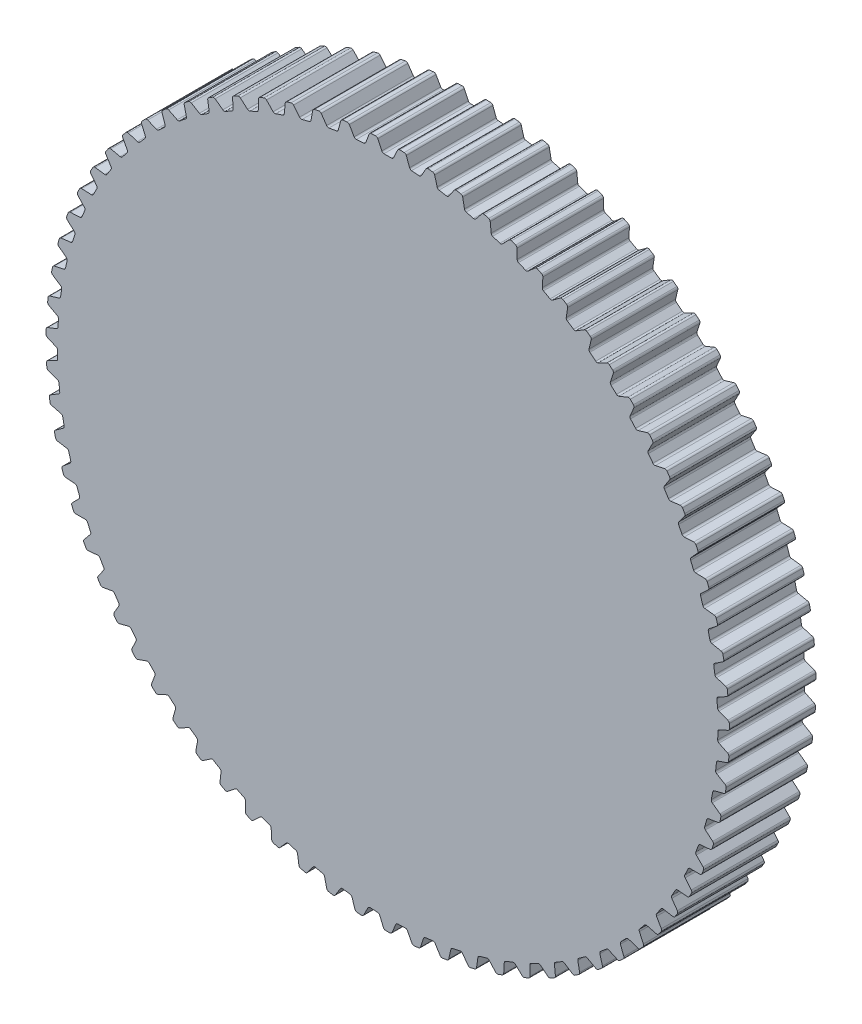
SolidWorks part; units mm, degrees
ref_plane "Ebene vorne" through (0, 0, 0) normal (0, 0, 1) x (1, 0, 0)
ref_plane "Ebene oben" through (0, 0, 0) normal (0, 1, 0) x (1, 0, 0)
ref_plane "Ebene rechts" through (0, 0, 0) normal (1, 0, 0) x (0, 0, -1)
ref_axis "Achse" through (0, 0, 4.125) along (0, 0, -1)
sketch "Skizze1" plane through (0, 0, 0) normal (0, 0, 1) x (1, 0, 0)
  circle A0 centre (0, 0) radius 29.6
  circle A1 centre (0, 0) radius 30.2 construction
  dimension "D1" = 0.6
  dimension "d0" = 59.2
  dimension "D2" = 60.4
extrude "Aufsatz-Linear austragen1" add sketch "Skizze1" along normal mid plane 7.5 contours A0 region at (0, 0, 0)
sketch "Skizze2" plane through (0, 0, 3.75) normal (0, 0, 1) x (1, 0, 0)
  line L0 (-0.8592, 29.4661) -> (-0.5091, 28.7155)
  line L1 (-0.3279, 28.6) -> (0.3279, 28.6)
  line L2 (0.5091, 28.7155) -> (0.8592, 29.4661)
  line L3 (0, 28.6) -> (0, 0) construction
  line L4 (-0.8592, 29.4661) -> (-0.915, 29.5859) construction
  line L5 (0.8592, 29.4661) -> (0.915, 29.5859) construction
  circle A0 centre (0, 0) radius 29.6 construction
  arc A1 (0.3279, 28.6) -> (0.5091, 28.7155) centre (0.3279, 28.8) ccw
  arc A2 (-0.5091, 28.7155) -> (-0.3279, 28.6) centre (-0.3279, 28.8) ccw
  arc A3 (-1.0475, 29.5815) -> (1.0475, 29.5815) centre (0, 0) ccw
  arc A4 (0.8592, 29.4661) -> (1.0475, 29.5815) centre (1.0404, 29.3816) cw
  arc A5 (-0.8592, 29.4661) -> (-1.0475, 29.5815) centre (-1.0404, 29.3816) ccw
  arc A6 (-1.0475, 29.5815) -> (1.0475, 29.5815) centre (0, 0) cw construction
  point P9 (0, 29.6)
  point P16 (0.915, 29.5859)
  point P19 (-0.915, 29.5859)
  dimension "D1" = 0.2
  dimension "hg" = 1
  dimension "alpha" = 25
  dimension "br" = 1.83
extrude "Schnitt-Linear austragen1" cut sketch "Skizze2" against normal through all flip side to cut
pattern_circular "Kreismuster3" count 75 over 360 about axis through (0, 0, 4.125) along (0, 0, -1) of "Schnitt-Linear austragen1"
